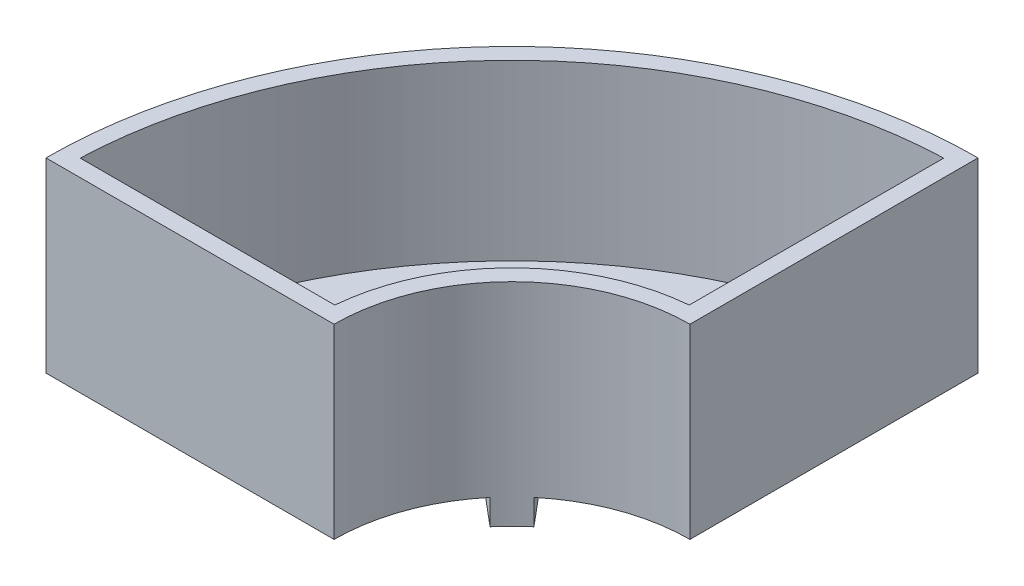
SolidWorks part; units mm, degrees
material "ABS"
ref_plane "Piano frontale" through (0, 0, 0) normal (0, 0, 1) x (1, 0, 0)
ref_plane "Piano superiore" through (0, 0, 0) normal (0, 1, 0) x (1, 0, 0)
ref_plane "Piano destro" through (0, 0, 0) normal (1, 0, 0) x (0, 0, -1)
sketch "Schizzo1" plane through (0, 0, 0) normal (0, 1, 0) x (1, 0, 0)
  line L0 (0, 0) -> (-110, 0) construction
  line L1 (0, 0) -> (0, 110) construction
  line L2 (-110, 0) -> (-42, 0)
  line L3 (0, 42) -> (0, 110)
  arc A0 (0, 110) -> (-110, 0) centre (0, 0) ccw
  arc A1 (0, 42) -> (-42, 0) centre (0, 0) ccw
  dimension "D1" = 220
  dimension "D2" = 42
extrude "Estrusione-Estrusione1" add sketch "Schizzo1" along normal blind 3
extrude "Estrusione-Sottile1" add sketch "Schizzo1<2>" along normal blind 44 thin thin type one direction reverse wall 4
sketch "Schizzo1<2>" plane through (0, 0, 0) normal (0, 1, 0) x (1, 0, 0) same geometry as "Schizzo1"
sketch "Schizzo2" plane through (0, 0, 0) normal (0, -1, 0) x (1, 0, 0)
  line L0 (0, 0) -> (-84.2649, -70.7066) construction
  line L1 (-70.7066, -84.2649) -> (0, 0) construction
  line L2 (-110, 0) -> (0, 0) construction
  line L3 (0, 0) -> (0, -110) construction
  line L4 (0, 0) -> (-77.7817, -77.7817) construction
  line L5 (-84.2649, -70.7066) -> (-32.1739, -26.9971)
  line L6 (-70.7066, -84.2649) -> (-26.9971, -32.1739)
  arc A0 (-110, 0) -> (0, -110) centre (0, 0) ccw construction
  arc A1 (-84.2649, -70.7066) -> (-70.7066, -84.2649) centre (0, 0) ccw
  arc A2 (-32.1739, -26.9971) -> (-26.9971, -32.1739) centre (0, 0) ccw
  dimension "D4" = 84
  dimension "D1" = 45
  dimension "D2" = 10
  dimension "D3" = 5
extrude "Estrusione-Estrusione2" add sketch "Schizzo2" along normal blind 6
